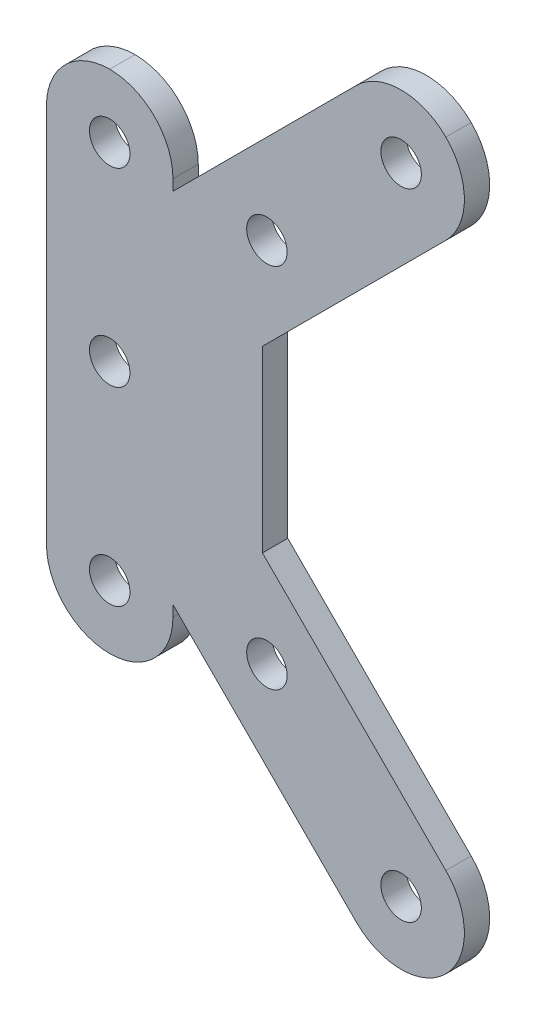
SolidWorks part; units mm, degrees
material "5052-O"
ref_plane "正面" through (0, 0, 0) normal (0, 0, 1) x (1, 0, 0)
ref_plane "平面" through (0, 0, 0) normal (0, 1, 0) x (1, 0, 0)
ref_plane "右側面" through (0, 0, 0) normal (1, 0, 0) x (0, 0, -1)
sketch "ｽｹｯﾁ1" plane through (0, 0, 0) normal (0, 0, 1) x (1, 0, 0)
  line L0 (-5, 20) -> (-5, -20)
  line L1 (-5, -20) -> (5, -20)
  line L2 (5, -20) -> (5, 20)
  line L3 (5, 20) -> (-5, 20)
  line L4 (5, 0) -> (30.1023, 25.1023)
  line L5 (30.1023, 25.1023) -> (23.0312, 32.1734)
  line L6 (23.0312, 32.1734) -> (5, 14.1421)
  line L7 (5, 0) -> (30.1023, -25.1023)
  line L8 (30.1023, -25.1023) -> (23.0312, -32.1734)
  line L9 (23.0312, -32.1734) -> (5, -14.1421)
  line L10 (5, 14.1421) -> (12.0711, 7.0711)
  line L11 (5, -14.1421) -> (12.0711, -7.0711)
  line L12 (12.0711, 7.0711) -> (12.0711, -7.0711)
  circle A0 centre (0, 0) radius 1.6
  circle A1 centre (0, 15) radius 1.6
  circle A2 centre (0, -15) radius 1.6
  dimension "D7" = 3.2
  dimension "D1" = 40
  dimension "D2" = 10
  dimension "D3" = 5
  dimension "D4" = 20
  dimension "D5" = 10
  dimension "D6" = 10
  dimension "D10" = 25.5
  dimension "D11" = 25.5
  dimension "D8" = 2
  dimension "D9" = 2
extrude "ﾎﾞｽ - 押し出し1" add sketch "ｽｹｯﾁ1" along normal mid plane 2 contours L6 L10 L4 L5 | L10 L2 L4 | L2 L11 L7 | L11 L9 L8 L7 | A1 | A0 | A2 | L12 L4 L7 | L0 L1 L2 L3 region at (7.357, 7.0711, 0) region at (17.5511, 19.6222, 0) region at (17.5511, -19.6222, 0) region at (7.357, -7.0711, 0) region at (9.714, 0, 0) region at (0, 0, 0) region at (0, 15, 0) region at (0, -15, 0)
sketch "ｽｹｯﾁ2" plane through (0, 0, 1) normal (0, 0, 1) x (1, 0, 0)
  line L0 (5, 14.1421) -> (12.0711, 7.0711)
  line L1 (12.0711, 7.0711) -> (30.1023, 25.1023) construction
  line L2 (5, -14.1421) -> (12.0711, -7.0711)
  line L3 (12.0711, -7.0711) -> (30.1023, -25.1023) construction
  line L4 (23.0312, 32.1734) -> (5, 14.1421) construction
  line L5 (55, 0) -> (-55, 0) construction
  circle A0 centre (12.4246, 14.4957) radius 1.6
  circle A1 centre (23.0312, 25.1023) radius 1.6
  circle A2 centre (12.4246, -14.4957) radius 1.6
  circle A3 centre (23.0312, -25.1023) radius 1.6
  dimension "D1" = 3.2
  dimension "D2" = 5.5
  dimension "D3" = 5
  dimension "D4" = 2
extrude "ｶｯﾄ - 押し出し1" cut sketch "ｽｹｯﾁ2" against normal through all contours A0 | A1 | A2 | A3
fillet "ﾌｨﾚｯﾄ1" radius 5 8 edges at (5, -20, 0) (-5, -20, 0) (23.0312, -32.1734, 0) (30.1023, -25.1023, 0) (30.1023, 25.1023, 0) (23.0312, 32.1734, 0) (5, 20, 0) (-5, 20, 0)
